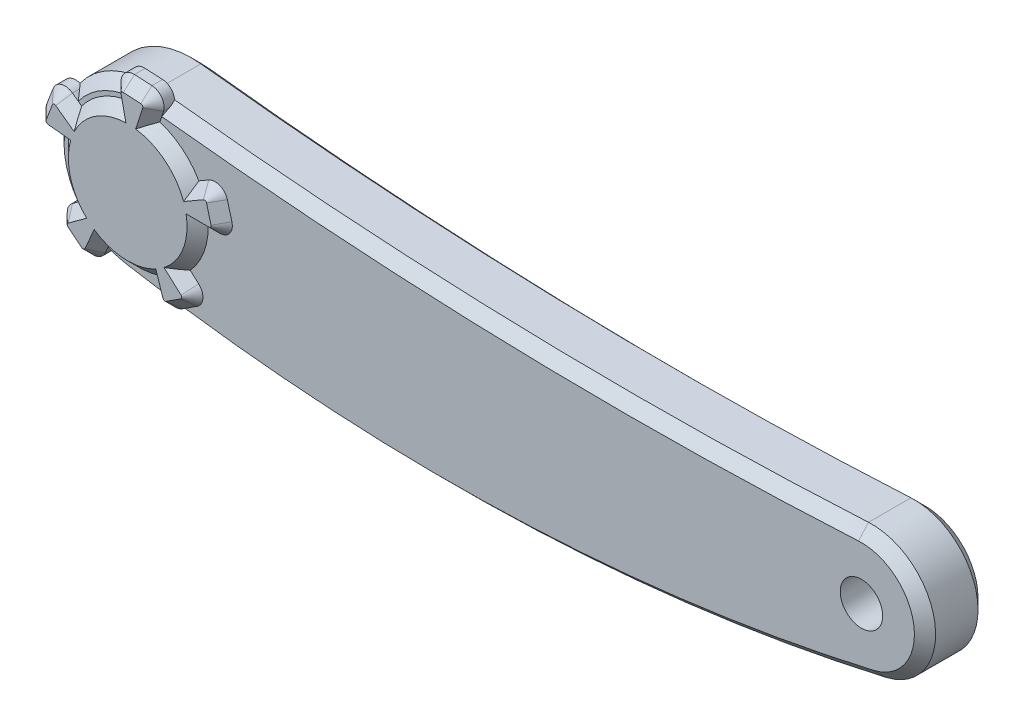
SolidWorks part; units mm, degrees
ref_plane "Front Plane" through (0, 0, 0) normal (0, 0, 1) x (1, 0, 0)
ref_plane "Top Plane" through (0, 0, 0) normal (0, 1, 0) x (1, 0, 0)
ref_plane "Right Plane" through (0, 0, 0) normal (1, 0, 0) x (0, 0, -1)
sketch "Sketch1" plane through (0, 0, 0) normal (0, 0, 1) x (1, 0, 0)
  line L0 (-85.28, 0) -> (85.28, 0)
  circle A0 centre (-85.28, 0) radius 20
  circle A1 centre (85.28, 0) radius 15
  arc A2 (-83.023, 19.8722) -> (84.4605, 14.9776) centre (29.8282, 1013.4841) ccw
  arc A3 (-88.6568, -19.7129) -> (88.6579, -14.6147) centre (-12.6788, 423.8267) ccw
  point P4 (0, 0)
sketch "Sketch3" plane through (0, 0, 0) normal (0, 0, 1) x (1, 0, 0)
extrude "Boss-Extrude2" add sketch "Sketch1" along normal mid plane 15 contours A2 A0 L0 A1 | A0 A3 A1 L0 | A0 | A1 region at (-1.0413, 7.6723, 0) region at (-72.7516, -14.857, 0) region at (-0.4576, -12.3881, 0) region at (74.6956, 10.0211, 0)
chamfer "Chamfer1" distance 2.5 angle 45 8 edges at (100.1314, 2.1065, -7.5) (0.6161, 13.9109, -7.5) (-105.0805, 2.818, -7.5) (0.2542, -25.9874, -7.5) (-105.0805, 2.818, 7.5) (0.6161, 13.9109, 7.5) (100.1314, 2.1065, 7.5) (0.2542, -25.9874, 7.5)
sketch "Sketch4" plane through (0, 0, 7.5) normal (0, 0, 1) x (1, 0, 0)
  circle A0 centre (-85.28, 0) radius 16.5
  circle A1 centre (85.28, 0) radius 9.8495
  dimension "D1" = 33
extrude "Boss-Extrude3" add sketch "Sketch4" along normal mid plane 5 contours A0
sketch "Sketch5" plane through (0, 0, 10) normal (0, 0, 1) x (1, 0, 0)
  line L0 (-85.28, 0) -> (-66.0957, 0)
  line L1 (-63.1979, 3.7765) -> (-64.2681, 7.7705)
  line L2 (-68.6659, 9.5922) -> (-85.28, 0)
  line L3 (-85.28, 0) -> (-63.733, 5.7735) construction
  line L4 (-71.0233, -12.8368) -> (-85.28, 0)
  line L5 (-85.28, 0) -> (-79.3517, -18.2454)
  line L6 (-74.8646, -19.8343) -> (-71.3967, -17.5823)
  line L7 (-93.083, -17.5258) -> (-85.28, 0)
  line L8 (-85.28, 0) -> (-100.8005, -11.2763)
  line L9 (-100.9251, -16.0348) -> (-97.7116, -18.637)
  line L10 (-104.3592, 2.0053) -> (-85.28, 0)
  line L11 (-85.28, 0) -> (-100.8005, 11.2763)
  line L12 (-105.3646, 9.9243) -> (-106.8464, 6.064)
  line L13 (-89.2687, 18.7651) -> (-85.28, 0)
  line L14 (-85.28, 0) -> (-79.3517, 18.2454)
  line L15 (-82.0479, 22.1683) -> (-86.1772, 22.3847)
  arc A0 (-63.1979, 3.7765) -> (-66.0957, 0) centre (-66.0957, 3) cw
  arc A1 (-68.6659, 9.5922) -> (-64.2681, 7.7705) centre (-67.1659, 6.9941) cw
  arc A2 (-71.0233, -12.8368) -> (-71.3967, -17.5823) centre (-73.0307, -15.0663) cw
  arc A3 (-74.8646, -19.8343) -> (-79.3517, -18.2454) centre (-76.4985, -17.3183) cw
  arc A4 (-93.083, -17.5258) -> (-97.7116, -18.637) centre (-95.8236, -16.3056) cw
  arc A5 (-100.9251, -16.0348) -> (-100.8005, -11.2763) centre (-99.0371, -13.7033) cw
  arc A6 (-104.3592, 2.0053) -> (-106.8464, 6.064) centre (-104.0457, 4.9889) cw
  arc A7 (-105.3646, 9.9243) -> (-100.8005, 11.2763) centre (-102.5638, 8.8492) cw
  arc A8 (-89.2687, 18.7651) -> (-86.1772, 22.3847) centre (-86.3342, 19.3888) cw
  arc A9 (-82.0479, 22.1683) -> (-79.3517, 18.2454) centre (-82.2049, 19.1724) cw
  circle A10 centre (-85.28, 0) radius 2
  point P10 (-65.28, 11.547)
  dimension "D3" = 3
  dimension "D6" = 4
  dimension "D1" = 30
  dimension "D2" = 20
  dimension "D4" = 19.1843
  dimension "D5" = 5
extrude "Boss-Extrude4" add sketch "Sketch5" against normal blind 5 contours L14 A9 L15 A8 L13 | L2 L0 A0 L1 A1 | L5 A3 L6 A2 L4 | L8 A5 L9 A4 L7 | L11 A7 L12 A6 L10
chamfer "Chamfer2" distance 2.5 angle 45 30 edges at (-69.8282, 8.9211, 10) (-66.0178, 9.7657, 10) (-63.733, 5.7735, 10) (-63.7156, 1.1737, 10) (-67.4378, 0, 10) (-69.8759, -5.9131, 10) (-72.0207, -11.9387, 10) (-70.0399, -15.3016, 10) (-73.1307, -18.7083, 10) (-77.5, -20.1463, 10) (-79.7665, -16.9689, 10) (-86.1435, -16.4774, 10) (-92.5371, -16.2996, 10) (-95.1233, -19.2227, 10) (-99.3183, -17.3359, 10) (-102.0361, -13.6248, 10) (-99.7146, -10.4874, 10) (-101.2178, -4.2705, 10) (-103.0244, 1.865, 10) (-106.6036, 3.4214, 10) (-106.1055, 7.9942, 10) (-103.4159, 11.7257, 10) (-99.7146, 10.4874, 10) (-94.2665, 13.8381, 10) (-88.9896, 17.4523, 10) (-88.6154, 21.3372, 10) (-84.1125, 22.2765, 10) (-79.7325, 20.8717, 10) (-79.7665, 16.9689, 10) (-74.8962, 12.8229, 10)
sketch "Sketch6" plane through (0, 0, 7.5) normal (0, 0, 1) x (1, 0, 0)
  circle A0 centre (85.28, 0) radius 5
  dimension "D1" = 10
extrude "Cut-Extrude1" cut sketch "Sketch6" against normal blind 10
sketch "Sketch7" plane through (0, 0, -7.5) normal (0, 0, -1) x (-1, 0, 0)
  circle A0 centre (85.28, 0) radius 5
  dimension "D1" = 10
extrude "Boss-Extrude5" add sketch "Sketch7" along normal blind 10
